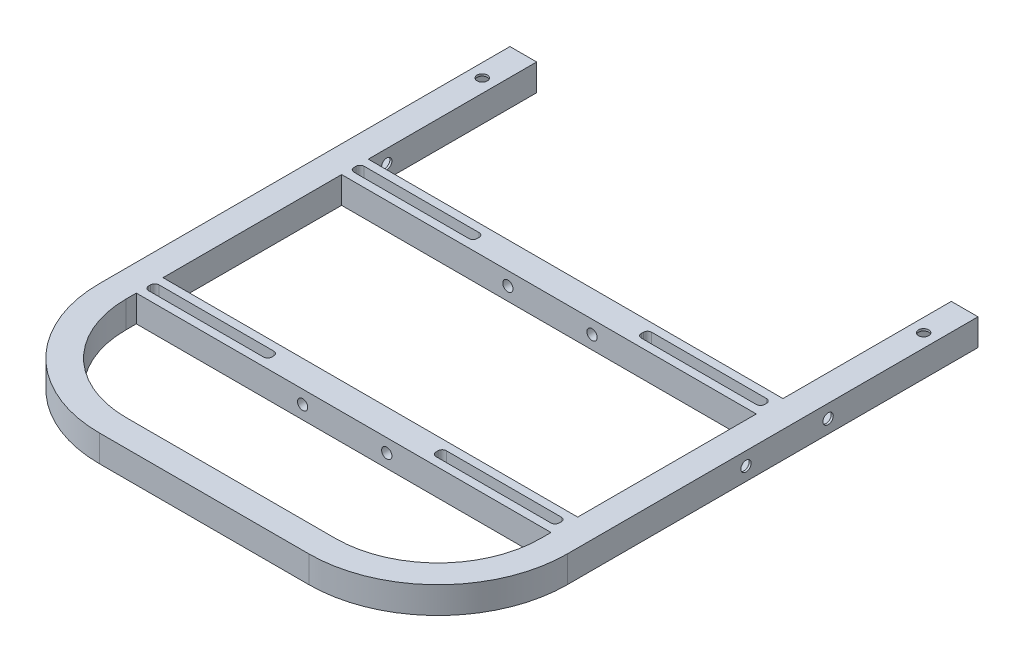
SolidWorks part; units mm, degrees
material "Plain Carbon Steel"
ref_plane "Front Plane" through (0, 0, 0) normal (0, 0, 1) x (1, 0, 0)
ref_plane "Top Plane" through (0, 0, 0) normal (0, 1, 0) x (1, 0, 0)
ref_plane "Right Plane" through (0, 0, 0) normal (1, 0, 0) x (0, 0, -1)
sketch "Sketch1" plane through (0, 0, 0) normal (0, 1, 0) x (1, 0, 0)
  line L0 (-256.54, 635) -> (-256.54, 127)
  line L1 (-129.54, 0) -> (129.54, 0)
  line L2 (256.54, 127) -> (256.54, 635)
  line L3 (-289.56, 635) -> (-289.56, 127)
  line L4 (-129.54, -33.02) -> (129.54, -33.02)
  line L5 (289.56, 127) -> (289.56, 635)
  line L6 (-256.54, 635) -> (-289.56, 635)
  line L7 (256.54, 635) -> (289.56, 635)
  arc A0 (129.54, 0) -> (256.54, 127) centre (129.54, 127) ccw
  arc A1 (-256.54, 127) -> (-129.54, 0) centre (-129.54, 127) ccw
  arc A2 (-289.56, 127) -> (-129.54, -33.02) centre (-129.54, 127) ccw
  arc A3 (129.54, -33.02) -> (289.56, 127) centre (129.54, 127) ccw
  point P8 (-256.54, 0)
  point P17 (0, 0)
  dimension "D3" = 127
  dimension "D1" = 579.12
  dimension "D2" = 635
  dimension "D4" = 33.02
extrude "Boss-Extrude1" add sketch "Sketch1" against normal blind 33.02
sketch "Sketch3" plane through (-256.54, 0, 0) normal (1, 0, 0) x (0, 0, -1)
  line L0 (127, -33.02) -> (635, -33.02) construction
  line L1 (139.7, 0) -> (172.72, 0)
  line L2 (139.7, 0) -> (139.7, -33.02)
  line L3 (139.7, -33.02) -> (172.72, -33.02)
  line L4 (172.72, 0) -> (172.72, -33.02)
  line L5 (139.7, 0) -> (172.72, -33.02) construction
  line L6 (139.7, -33.02) -> (172.72, 0) construction
  line L7 (127, -33.02) -> (127, 0) construction
  point P0 (156.21, -16.51)
  point P7 (139.7, -16.51)
  dimension "D1" = 12.7
  dimension "D2" = 33.02
  dimension "D3" = 33.02
extrude "Boss-Extrude2" add sketch "Sketch3" along normal up to next
sketch "Sketch5" plane through (0, 0, 0) normal (0, 1, 0) x (1, 0, 0)
  line L0 (-256.54, 172.72) -> (-256.54, 635) construction
  line L1 (-251.46, 162.56) -> (-109.22, 162.56)
  line L2 (-256.54, 157.48) -> (-256.54, 154.94)
  line L3 (-251.46, 149.86) -> (-109.22, 149.86)
  line L4 (-104.14, 157.48) -> (-104.14, 154.94)
  line L5 (-256.54, 162.56) -> (-104.14, 149.86) construction
  line L6 (-256.54, 149.86) -> (-104.14, 162.56) construction
  line L7 (256.54, 172.72) -> (-256.54, 172.72) construction
  line L10 (99.06, 157.48) -> (99.06, 154.94)
  line L11 (104.14, 162.56) -> (246.38, 162.56)
  line L12 (251.46, 157.48) -> (251.46, 154.94)
  line L13 (104.14, 149.86) -> (246.38, 149.86)
  line L14 (256.54, 139.7) -> (256.54, 127) construction
  line L15 (256.54, 139.7) -> (-256.54, 139.7) construction
  arc A0 (-109.22, 149.86) -> (-104.14, 154.94) centre (-109.22, 154.94) ccw
  arc A1 (-104.14, 157.48) -> (-109.22, 162.56) centre (-109.22, 157.48) ccw
  arc A2 (-256.54, 154.94) -> (-251.46, 149.86) centre (-251.46, 154.94) ccw
  arc A3 (-251.46, 162.56) -> (-256.54, 157.48) centre (-251.46, 157.48) ccw
  arc A4 (104.14, 162.56) -> (99.06, 157.48) centre (104.14, 157.48) ccw
  arc A5 (99.06, 154.94) -> (104.14, 149.86) centre (104.14, 154.94) ccw
  arc A6 (251.46, 157.48) -> (246.38, 162.56) centre (246.38, 157.48) ccw
  arc A7 (246.38, 149.86) -> (251.46, 154.94) centre (246.38, 154.94) ccw
  point P0 (-180.34, 156.21)
  dimension "D5" = 5.08
  dimension "D1" = 0
  dimension "D2" = 12.7
  dimension "D3" = 10.16
  dimension "D4" = 152.4
  dimension "D7" = 203.2
  dimension "D6" = 2
extrude "Cut-Extrude1" cut sketch "Sketch5" against normal through all
sketch "Sketch6" plane through (0, 0, -172.72) normal (0, 0, -1) x (-1, 0, 0)
  line L0 (-256.54, 0) -> (-256.54, -33.02) construction
  line L1 (-256.54, 0) -> (256.54, 0) construction
  circle A0 centre (50.8, -16.51) radius 6.35
  circle A1 centre (-53.34, -16.51) radius 6.35
  dimension "D1" = 12.7
  dimension "D3" = 50.8
  dimension "D4" = 203.2
  dimension "D5" = 16.51
  dimension "D2" = 2
extrude "Cut-Extrude2" cut sketch "Sketch6" against normal up to next
pattern_linear "LPattern1" count 2 spacing 254 along (0, 0, -1) of "Boss-Extrude2", "Cut-Extrude1", "Cut-Extrude2"
shell "Shell1" thickness 2.54 removed face at (273.05, -16.51, -635)
sketch "Sketch7" plane through (0, 0, -635) normal (0, 0, -1) x (-1, 0, 0)
  line L8 (287.02, -2.54) -> (259.08, -2.54)
  line L9 (259.08, -2.54) -> (259.08, -30.48)
  line L10 (259.08, -30.48) -> (287.02, -30.48)
  line L11 (287.02, -30.48) -> (287.02, -2.54)
  line L12 (287.02, -2.54) -> (259.08, -2.54)
  line L13 (259.08, -2.54) -> (259.08, -30.48)
  line L14 (259.08, -30.48) -> (287.02, -30.48)
  line L15 (287.02, -30.48) -> (287.02, -2.54)
  dimension "D1" = 2.54
extrude "Cut-Extrude3" cut sketch "Sketch7" against normal up to next
sketch "Sketch8" plane through (0, 0, 0) normal (0, 1, 0) x (1, 0, 0)
  line L0 (-256.54, 635) -> (-289.56, 635) construction
  line L1 (0, -18.161) -> (0, 18.161) construction
  circle A0 centre (-273.05, 584.2) radius 6.35
  circle A1 centre (273.05, 584.2) radius 6.35
  point P9 (-273.05, 635)
  dimension "D1" = 12.7
  dimension "D2" = 50.8
extrude "Cut-Extrude4" cut sketch "Sketch8" against normal up to next
sketch "Sketch9" plane through (289.56, 0, 0) normal (1, 0, 0) x (0, 0, -1)
  circle A0 centre (347.98, -16.51) radius 6.35
  circle A1 centre (449.58, -16.51) radius 6.35
  dimension "D1" = 12.7
extrude "Cut-Extrude5" cut sketch "Sketch9" against normal up to next
sketch "Sketch10" plane through (-289.56, 0, 0) normal (-1, 0, 0) x (0, 0, 1)
  circle A1 centre (-347.98, -16.51) radius 6.35
  dimension "D1" = 12.7
extrude "Cut-Extrude6" cut sketch "Sketch10" against normal up to next
sketch "Sketch11" plane through (0, 0, 0) normal (0, 1, 0) x (1, 0, 0)
  line L11 (-289.56, 177.8) -> (-340.36, 177.8)
  line L12 (-340.36, 228.6) -> (-340.36, 177.8)
  line L13 (-289.56, 228.6) -> (-340.36, 228.6)
  line L14 (-289.56, 228.6) -> (-289.56, 177.8)
  line L15 (289.56, 228.6) -> (289.56, 177.8)
  line L16 (289.56, 228.6) -> (340.36, 228.6)
  line L17 (340.36, 228.6) -> (340.36, 177.8)
  line L18 (289.56, 177.8) -> (340.36, 177.8)
  line L19 (256.54, 393.7) -> (256.54, 172.72) construction
  line L20 (256.54, 393.7) -> (-256.54, 393.7) construction
  dimension "D1" = 33.02
  dimension "D2" = 83.82
  dimension "D3" = 546.1
  dimension "D4" = 165.1
extrude "Boss-Extrude3" [suppressed] add sketch "Sketch11" against normal blind 25.4 separate body
sketch "Sketch13" [suppressed] plane through (0, 0, 0) normal (0, 1, 0) x (1, 0, 0)
  line L0 (-289.56, 177.8) -> (-289.56, 228.6) construction
  line L1 (-289.56, 228.6) -> (-340.36, 228.6) construction
  circle A0 centre (-314.96, 203.2) radius 8.001
  dimension "D1" = 16.002
  dimension "D2" = 25.4
  dimension "D3" = 25.4
extrude "Cut-Extrude8" [suppressed] cut sketch "Sketch13" against normal through all
sketch "Sketch14" [suppressed] plane through (0, 0, 0) normal (0, 1, 0) x (1, 0, 0)
  circle A0 centre (314.96, 203.2) radius 8.382
  dimension "D1" = 16.764
extrude "Cut-Extrude9" [suppressed] cut sketch "Sketch14" against normal through all
sketch "Sketch15" plane through (256.54, 0, 0) normal (-1, 0, 0) x (0, 0, 1)
  circle A0 centre (-449.58, -16.51) radius 6.35
  dimension "D1" = 12.7
extrude "Cut-Extrude10" cut sketch "Sketch15" against normal through all
sketch "Sketch16" plane through (-289.56, 0, 0) normal (-1, 0, 0) x (0, 0, 1)
  circle A0 centre (-449.58, -16.51) radius 6.35
  dimension "D1" = 12.7
extrude "Cut-Extrude11" cut sketch "Sketch16" against normal through all
sketch "Sketch18" [suppressed] plane through (0, 0, 0) normal (0, 1, 0) x (1, 0, 0)
  line L0 (340.36, 177.8) -> (340.36, 228.6) construction
  line L1 (289.56, 190.5) -> (340.36, 190.5)
  line L2 (289.56, 190.5) -> (289.56, 215.9)
  line L3 (289.56, 215.9) -> (340.36, 215.9)
  line L4 (340.36, 190.5) -> (340.36, 215.9)
  line L5 (289.56, 190.5) -> (340.36, 215.9) construction
  line L6 (289.56, 215.9) -> (340.36, 190.5) construction
  line L7 (340.36, 228.6) -> (289.56, 228.6) construction
  point P0 (314.96, 203.2)
  dimension "D1" = 12.7
extrude "Cut-Extrude12" [suppressed] cut sketch "Sketch18" against normal blind 30.988
fillet "Fillet1" [suppressed] type full round
fillet "Fillet2" [suppressed] type full round
sketch "Sketch19" [suppressed] plane through (0, 0, 0) normal (0, 1, 0) x (1, 0, 0)
  line L5 (-289.56, 177.8) -> (-289.56, 228.6) construction
  line L6 (-340.36, 215.9) -> (-289.56, 215.9)
  line L10 (-340.36, 215.9) -> (-340.36, 190.5)
  line L11 (-340.36, 190.5) -> (-289.56, 190.5)
  line L12 (-289.56, 215.9) -> (-289.56, 190.5)
  line L13 (-340.36, 215.9) -> (-289.56, 190.5) construction
  line L14 (-340.36, 190.5) -> (-289.56, 215.9) construction
  line L15 (-289.56, 228.6) -> (-340.36, 228.6) construction
  point P0 (-311.785, 205.0653)
  point P1 (-314.96, 203.2)
  dimension "D1" = 12.7
extrude "Cut-Extrude13" [suppressed] cut sketch "Sketch19" against normal blind 53.34
fillet "Fillet3" [suppressed] type full round
fillet "Fillet4" [suppressed] type full round
